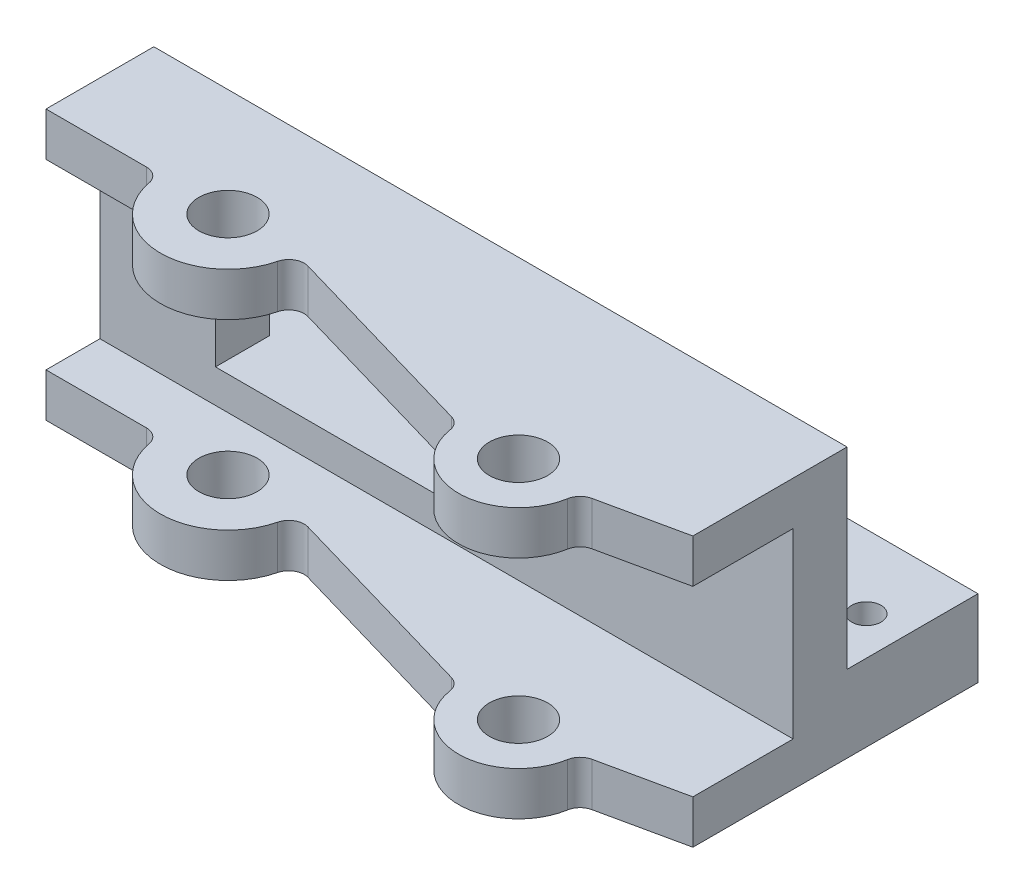
SolidWorks part; units mm, degrees
ref_plane "Front Plane" through (0, 0, 0) normal (0, 0, 1) x (1, 0, 0)
ref_plane "Top Plane" through (0, 0, 0) normal (0, 1, 0) x (1, 0, 0)
ref_plane "Right Plane" through (0, 0, 0) normal (1, 0, 0) x (0, 0, -1)
sketch "Sketch1" plane through (0, 0, 0) normal (0, 0, 1) x (1, 0, 0)
  line L1 (57.15, -22.225) -> (-57.15, -22.225)
  line L2 (57.15, -22.225) -> (57.15, 22.225)
  line L3 (57.15, 22.225) -> (-57.15, 22.225)
  line L4 (-57.15, -22.225) -> (-57.15, 22.225)
  line L5 (57.15, -22.225) -> (-57.15, 22.225) construction
  line L6 (57.15, 22.225) -> (-57.15, -22.225) construction
  point P0 (0, 0)
  dimension "D1" = 44.45
  dimension "D2" = 114.3
extrude "Boss-Extrude1" add sketch "Sketch1" along normal blind 62.23
sketch "Sketch2" plane through (0, 0, 62.23) normal (0, 0, 1) x (1, 0, 0)
  line L0 (-57.15, 22.225) -> (-57.15, -22.225) construction
  line L1 (57.15, -15.025) -> (-57.15, -15.025)
  line L2 (57.15, -15.025) -> (57.15, 15.025)
  line L3 (57.15, 15.025) -> (-57.15, 15.025)
  line L4 (-57.15, -15.025) -> (-57.15, 15.025)
  line L5 (57.15, -15.025) -> (-57.15, 15.025) construction
  line L6 (57.15, 15.025) -> (-57.15, -15.025) construction
  line L7 (57.15, 22.225) -> (-57.15, 22.225) construction
  point P0 (0, 0)
  dimension "D1" = 7.2
extrude "Cut-Extrude2" cut sketch "Sketch2" against normal blind 31.75
sketch "Sketch3" plane through (0, 0, 0) normal (0, 0, -1) x (-1, 0, 0)
  line L0 (-57.15, -22.225) -> (-57.15, 22.225) construction
  line L1 (57.15, 22.225) -> (-57.15, 22.225)
  line L2 (57.15, 22.225) -> (57.15, -9.525)
  line L3 (57.15, -9.525) -> (-57.15, -9.525)
  line L4 (-57.15, 22.225) -> (-57.15, -9.525)
  line L5 (57.15, -22.225) -> (-57.15, -22.225) construction
  dimension "D1" = 12.7
extrude "Cut-Extrude3" cut sketch "Sketch3" against normal blind 21.59
sketch "Sketch5" plane through (0, -22.225, 0) normal (0, -1, 0) x (1, 0, 0)
  line L0 (0, 12.06) -> (50.8, 12.06) construction
  line L1 (57.15, 21.59) -> (-57.15, 21.59) construction
  line L2 (57.15, 62.23) -> (57.15, 0) construction
  circle A0 centre (0, 12.06) radius 2.415
  circle A1 centre (50.8, 12.06) radius 2.415
  dimension "D3" = 4.83
  dimension "D4" = 6.35
  dimension "D1" = 9.53
  dimension "D2" = 50.8
extrude "Cut-Extrude4" cut sketch "Sketch5" against normal blind 25.4
sketch "Sketch6" plane through (0, 0, 21.59) normal (0, 0, -1) x (-1, 0, 0)
  line L0 (-53.215, -9.525) -> (2.415, -9.525) construction
  line L1 (-53.215, -9.525) -> (-53.215, -22.225) construction
  line L2 (2.415, -22.225) -> (2.415, -9.525) construction
  line L3 (-57.15, -9.525) -> (57.15, -9.525) construction
  line L4 (-30.6705, 6.477) -> (-30.6705, 1.651) construction
  line L5 (-32.893, 6.477) -> (-17.907, 6.477) construction
  line L6 (-22.987, 1.651) -> (-32.893, 1.651) construction
  line L7 (-32.893, 1.651) -> (-32.893, 6.477) construction
  circle A1 centre (-30.6705, 4.064) radius 2.2225
  dimension "D3" = 4.445
extrude "Cut-Extrude5" cut sketch "Sketch6" against normal blind 5.08
sketch "Sketch7" plane through (0, -22.225, 0) normal (0, -1, 0) x (1, 0, 0)
  line L0 (57.15, 62.23) -> (57.15, 0) construction
  line L1 (-57.15, 0) -> (57.15, 0) construction
  circle A0 centre (31.75, 50.36) radius 4.8
  circle A1 centre (-27.14, 39.37) radius 4.8
  dimension "D1" = 9.6
  dimension "D2" = 25.4
  dimension "D3" = 39.37
  dimension "D4" = 9.6
  dimension "D5" = 58.89
  dimension "D6" = 10.99
extrude "Cut-Extrude6" cut sketch "Sketch7" against normal up to surface (44.45 mm away) up to face at (0, 22.225, 41.91)
sketch "Sketch9" plane through (0, 0, 30.48) normal (0, 0, 1) x (1, 0, 0)
  line L5 (57.15, 15.025) -> (-57.15, 15.025) construction
  line L6 (-38.1, 15.025) -> (6.35, 15.025)
  line L7 (-38.1, 15.025) -> (-38.1, -15.025)
  line L8 (-38.1, -15.025) -> (6.35, -15.025)
  line L9 (6.35, 15.025) -> (6.35, -15.025)
  line L10 (-57.15, -15.025) -> (57.15, -15.025) construction
  line L11 (-57.15, 15.025) -> (-57.15, -15.025) construction
  line L12 (57.15, -15.025) -> (57.15, 15.025) construction
  dimension "D1" = 50.8
  dimension "25in" = 19.05
extrude "Cut-Extrude7" cut sketch "Sketch9" against normal through all both and the other way through all
sketch "Sketch14" plane through (6.35, 0, 0) normal (-1, 0, 0) x (0, 0, 1)
  line L0 (0, -15.025) -> (30.48, -15.025) construction
  line L1 (21.59, -9.525) -> (0, -9.525)
  line L2 (21.59, -9.525) -> (21.59, -15.025)
  line L3 (21.59, -15.025) -> (0, -15.025)
  line L4 (0, -9.525) -> (0, -15.025)
extrude "Boss-Extrude2" add sketch "Sketch14" along normal up to next
sketch "Sketch16" plane through (0, -22.225, 0) normal (0, -1, 0) x (1, 0, 0)
  line L8 (-57.15, 62.23) -> (57.15, 62.23)
  line L9 (57.15, 62.23) -> (57.15, 47.0103)
  line L10 (57.15, 62.23) -> (57.15, 0) construction
  line L11 (-15.99, 39.37) -> (21.87, 50.36)
  line L12 (41.63, 50.36) -> (57.15, 47.0103)
  line L13 (-38.29, 39.37) -> (-57.15, 39.37)
  line L14 (-57.15, 62.23) -> (-57.15, 0) construction
  line L15 (-57.15, 39.37) -> (-57.15, 62.23)
  arc A2 (41.63, 50.36) -> (21.87, 50.36) centre (31.75, 50.36) ccw
  arc A3 (-15.99, 39.37) -> (-38.29, 39.37) centre (-27.14, 39.37) ccw
  circle A4 centre (-27.14, 39.37) radius 4.8 construction
  circle A5 centre (31.75, 50.36) radius 4.8 construction
  dimension "D1" = 6.35
  dimension "D2" = 5.08
extrude "Cut-Extrude8" cut sketch "Sketch16" against normal through all
fillet "Fillet1" radius 2.54 8 edges at (21.87, 18.625, 50.36) (41.63, -18.625, 50.36) (41.63, 18.625, 50.36) (-15.99, 18.625, 39.37) (-15.99, -18.625, 39.37) (21.87, -18.625, 50.36) (-38.29, -18.625, 39.37) (-38.29, 18.625, 39.37)
sketch "Sketch17" plane through (0, 0, 21.59) normal (0, 0, 1) x (1, 0, 0)
  line L1 (6.35, -15.025) -> (-38.1, -15.025)
  line L2 (6.35, -15.025) -> (6.35, -9.525)
  line L3 (6.35, -9.525) -> (-38.1, -9.525)
  line L4 (-38.1, -15.025) -> (-38.1, -9.525)
extrude "Boss-Extrude3" add sketch "Sketch17" along normal up to surface (8.89 mm away) up to face at (-47.625, 0, 30.48)
